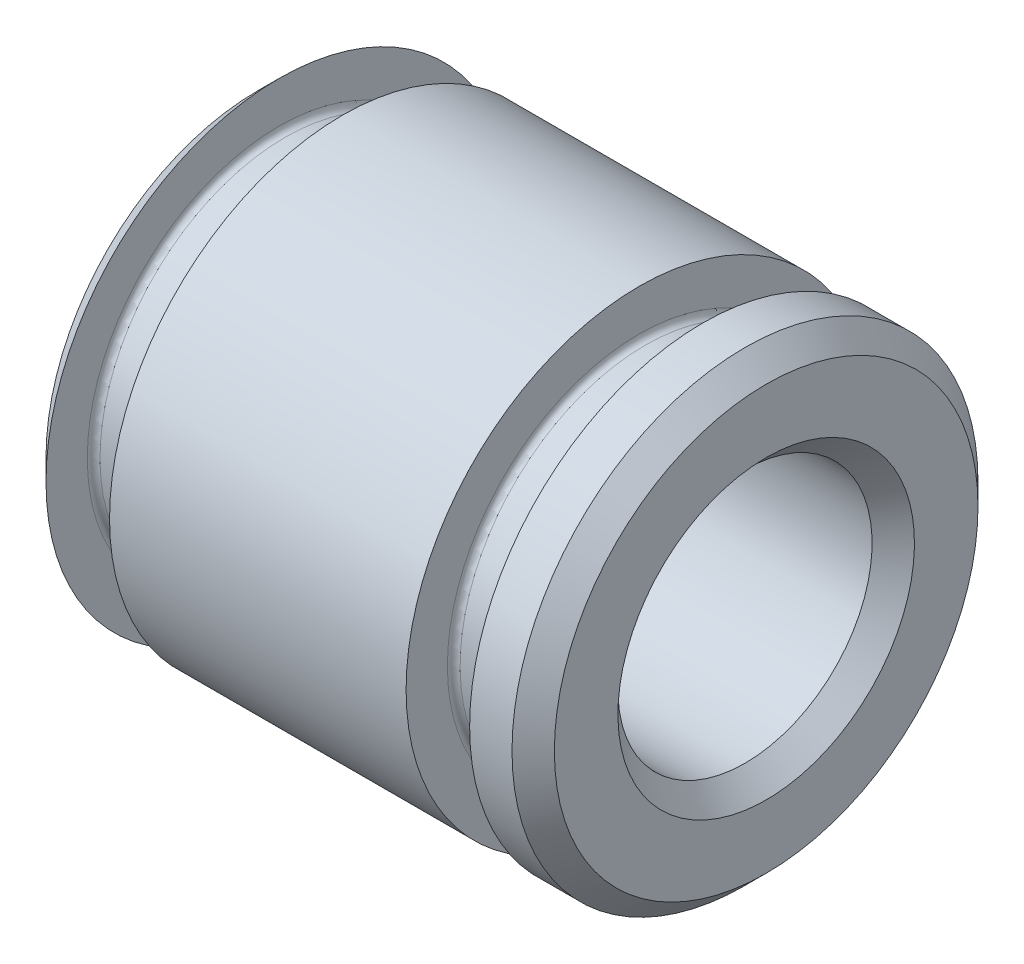
SolidWorks part; units mm, degrees
material "Acciaio al carbonio semplice"
ref_plane "Piano frontale" through (0, 0, 0) normal (0, 0, 1) x (1, 0, 0)
ref_plane "Piano superiore" through (0, 0, 0) normal (0, 1, 0) x (1, 0, 0)
ref_plane "Piano destro" through (0, 0, 0) normal (1, 0, 0) x (0, 0, -1)
sketch "Schizzo1" plane through (0, 0, 0) normal (0, 0, 1) x (1, 0, 0)
  line L0 (0, 0) -> (0, 11)
  line L2 (24, 11) -> (24, 0)
  line L3 (24, 0) -> (0, 0) construction
  line L8 (21, 11) -> (24, 11)
  line L9 (0, 0) -> (24, 0) construction
  line L10 (18, 11) -> (18, 8.75)
  line L11 (18, 8.75) -> (21, 8.75)
  line L12 (21, 8.75) -> (21, 11)
  line L13 (24, 0) -> (0, 0)
  line L15 (1, 8.75) -> (4, 8.75)
  line L16 (4, 8.75) -> (4, 11)
  line L17 (4, 11) -> (18, 11)
  line L18 (0, 11) -> (1, 11)
  line L19 (1, 11) -> (1, 8.75)
  line L20 (0, 0) -> (-4.0571, 0) construction
  dimension "D1" = 17.5
  dimension "D2" = 3
  dimension "D3" = 3
  dimension "D4" = 22
  dimension "D5" = 24
  dimension "D6" = 1
revolve "Rivoluzione1" add sketch "Schizzo1" angle 360 about L3
sketch "Schizzo2" plane through (24, 0, 0) normal (1, 0, 0) x (0, 0, -1)
  circle A0 centre (0, 0) radius 6
  dimension "D1" = 12
extrude "Taglio-Estrusione1" cut sketch "Schizzo2" against normal blind 21
chamfer "Smusso1" distance 1 angle 45 2 edges at (24, 11, 0) (0, 11, 0)
fillet "Raccordo1" radius 0.3 4 edges at (21, 8.75, 0) (18, 8.75, 0) (4, 8.75, 0) (1, 8.75, 0)
chamfer "Smusso2" distance 1 angle 45 1 edges at (24, 6, 0)
